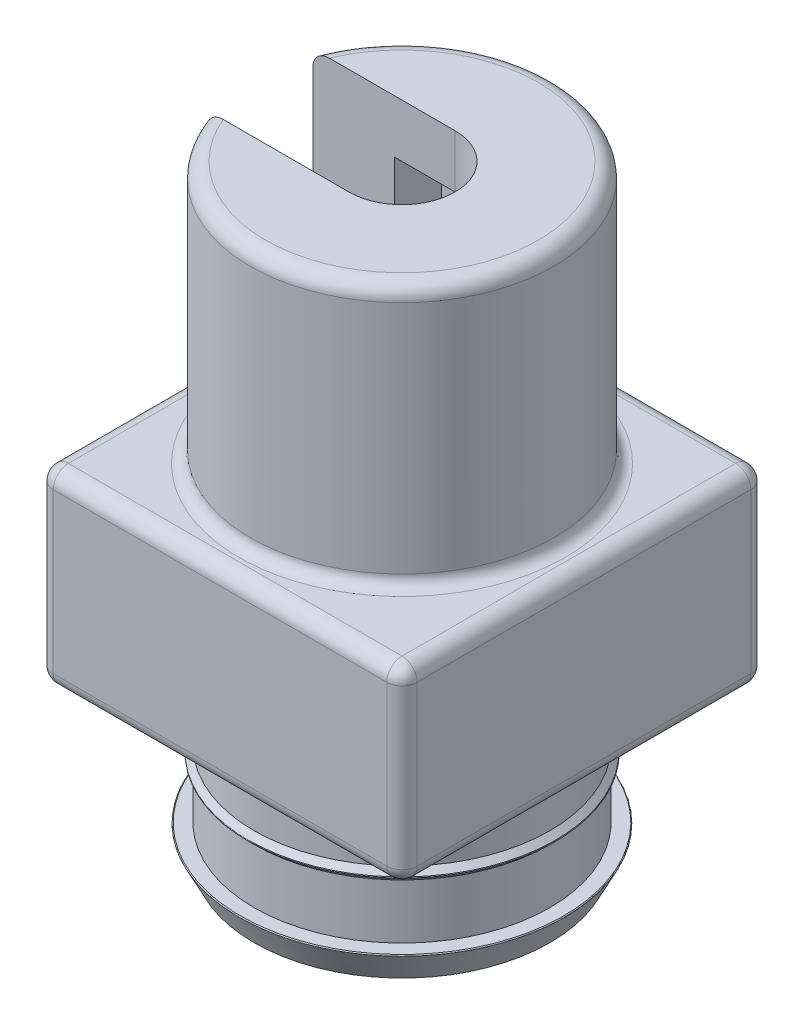
SolidWorks part; units mm, degrees
ref_plane "Front Plane" through (0, 0, 0) normal (0, 0, 1) x (1, 0, 0)
ref_plane "Top Plane" through (0, 0, 0) normal (0, 1, 0) x (1, 0, 0)
ref_plane "Right Plane" through (0, 0, 0) normal (1, 0, 0) x (0, 0, -1)
sketch "Sketch1" plane through (0, 0, 0) normal (0, 0, 1) x (1, 0, 0)
  line L0 (0, 1017.6623) -> (0, 12.7) construction
  line L1 (0, -12.7) -> (19.5, -12.7)
  line L8 (0, 7.3) -> (0, -12.7)
  line L9 (19.5, -12.7) -> (21.5, -8.7)
  line L25 (7.9375, 6.35) -> (0, 6.35) construction
  line L32 (21.5, -8.7) -> (19.5, -8.7)
  line L33 (19.5, -8.7) -> (19.5, -1.4938)
  line L34 (19.5, 0.0938) -> (20.2938, -0.7)
  line L35 (20.2938, -0.7) -> (19.5, -1.4938)
  line L36 (20.2938, -0.7) -> (9.4, -0.7) construction
  line L40 (0, 7.3) -> (0, -7.7377) construction
  line L41 (0, 7.3) -> (19.5, 7.3)
  line L42 (19.5, 7.3) -> (19.5, 0.0938)
  dimension "D7" = 2
  dimension "D4" = 16
  dimension "D2" = 4
  dimension "D3" = 19.5
  dimension "D5" = 0.7937
  dimension "D10" = 12
  dimension "D11" = 45
  dimension "D9" = 0.7937
revolve "Revolve1" add sketch "Sketch1" angle 360 about L0
fillet "Fillet4" radius 0.0992 2 edges at (0, -8.7, 21.5) (0, -0.7, 20.2938)
ref_plane "Plane1" through (0, 7.3, 0) normal (0, 1, 0) x (1, 0, 0)
sketch "Sketch2" plane through (0, 7.3, 0) normal (0, 1, 0) x (1, 0, 0)
  line L0 (0, 9.6273) -> (0, -9.6273) construction
  line L9 (9.0227, 0) -> (-9.0227, 0) construction
  line L11 (24, 24) -> (-24, 24)
  line L12 (24, 24) -> (24, -24)
  line L13 (24, -24) -> (-24, -24)
  line L14 (-24, 24) -> (-24, -24)
  line L15 (24, 24) -> (-24, -24) construction
  line L16 (24, -24) -> (-24, 24) construction
  point P0 (0, 0)
  point P1 (0, 0)
  point P2 (0, 0)
  point P6 (0, 0)
  point P11 (0, 0)
  dimension "D1" = 48
  dimension "D2" = 48
extrude "Boss-Extrude1" add sketch "Sketch2" along normal blind 25
sketch "Sketch3" plane through (0, -12.7, 0) normal (0, -1, 0) x (1, 0, 0)
  circle A0 centre (0, 0) radius 2.413
extrude "Cut-Extrude1" cut sketch "Sketch3" against normal blind 32
sketch "Sketch5" plane through (0, 0, 0) normal (1, 0, 0) x (0, 0, -1)
  line L0 (0, 32.3) -> (0, 7.3) construction
  line L1 (24, 32.3) -> (-24, 32.3) construction
  line L2 (21.45, 7.3) -> (-21.45, 7.3) construction
  circle A0 centre (0, 19.8) radius 2
  dimension "D1" = 4
extrude "Cut-Extrude3" cut sketch "Sketch5" against normal through all and the other way blind 2.3
sketch "Sketch7" plane through (0, 32.3, 0) normal (0, 1, 0) x (1, 0, 0)
  circle A0 centre (0, 0) radius 20
  dimension "D1" = 40
extrude "Boss-Extrude2" add sketch "Sketch7" along normal blind 7.5
sketch "Sketch8" plane through (0, 39.8, 0) normal (0, 1, 0) x (1, 0, 0)
  circle A0 centre (0, 0) radius 12.5
  circle A1 centre (0, 0) radius 20
  circle A2 centre (0, 0) radius 20
  dimension "D1" = 0
extrude "Boss-Extrude3" add sketch "Sketch8" along normal blind 12
ref_plane "Plane2" through (0, 51.8, 0) normal (0, 1, 0) x (1, 0, 0)
sketch "Sketch9" plane through (0, 51.8, 0) normal (0, 1, 0) x (1, 0, 0)
  circle A1 centre (0, 0) radius 20
  circle A2 centre (0, 0) radius 20
  dimension "D1" = 0
extrude "Boss-Extrude4" add sketch "Sketch9" along normal blind 15
sketch "Sketch10" plane through (0, 51.8, 0) normal (0, 1, 0) x (1, 0, 0)
  line L1 (-6.5547, -10.1998) -> (5.556, -10.7764)
  line L2 (5.556, -10.7764) -> (12.1106, -0.5766)
  line L3 (12.1106, -0.5766) -> (6.5547, 10.1998)
  line L4 (6.5547, 10.1998) -> (-5.556, 10.7764)
  line L5 (-5.556, 10.7764) -> (-12.1106, 0.5766)
  line L6 (-12.1106, 0.5766) -> (-6.5547, -10.1998)
  circle A0 centre (0, 0) radius 10.5 construction
  dimension "D1" = 21
extrude "Cut-Extrude4" cut sketch "Sketch10" along normal blind 8
sketch "Sketch11" plane through (0, 0, 0) normal (1, 0, 0) x (0, 0, -1)
  line L0 (0, 66.8) -> (0, 23.9688) construction
  line L1 (20, 66.8) -> (-20, 66.8) construction
  line L3 (7, 51.8) -> (12.5, 51.8)
  line L5 (-7, 51.8) -> (-7, 66.8)
  line L6 (-7, 66.8) -> (7, 66.8)
  line L7 (7, 51.8) -> (7, 66.8)
  line L8 (-7, 51.8) -> (7, 66.8) construction
  line L9 (-7, 66.8) -> (7, 51.8) construction
  line L10 (-12.5, 41.8) -> (12.5, 41.8)
  line L11 (-12.5, 41.8) -> (-12.5, 51.8)
  line L12 (-12.5, 51.8) -> (-7, 51.8)
  line L13 (12.5, 41.8) -> (12.5, 51.8)
  line L14 (-12.5, 41.8) -> (12.5, 51.8) construction
  line L15 (-12.5, 51.8) -> (12.5, 41.8) construction
  point P6 (0, 59.3)
  point P11 (0, 46.8)
  dimension "D1" = 14
  dimension "D3" = 10
  dimension "D4" = 25
extrude "Cut-Extrude5" cut sketch "Sketch11" against normal through all
sketch "Sketch12" plane through (0, 66.8, 0) normal (0, 1, 0) x (1, 0, 0)
  circle A0 centre (0, 0) radius 7
  dimension "D1" = 14
extrude "Cut-Extrude6" cut sketch "Sketch12" against normal blind 12 and the other way through all
fillet "Fillet16" radius 1 5 edges at (-7.8062, 51.8, -12.5) (0, 39.8, 12.5) (-7.8062, 51.8, 12.5) (-7.8062, 41.8, 12.5) (12.5, 51.8, 0)
fillet "Fillet18" radius 2 13 edges at (24, 19.8, 24) (0, 7.3, 24) (-24, 19.8, 24) (-24, 19.8, -24) (24, 19.8, -24) (24, 7.3, 0) (0, 7.3, -24) (-24, 7.3, 0) (0, 32.3, 24) (24, 32.3, 0) (0, 32.3, -24) (-24, 32.3, 0) (20, 66.8, 0)
fillet "Fillet20" radius 1.5 2 edges at (0, 7.3, 19.5) (0, 32.3, 20)
